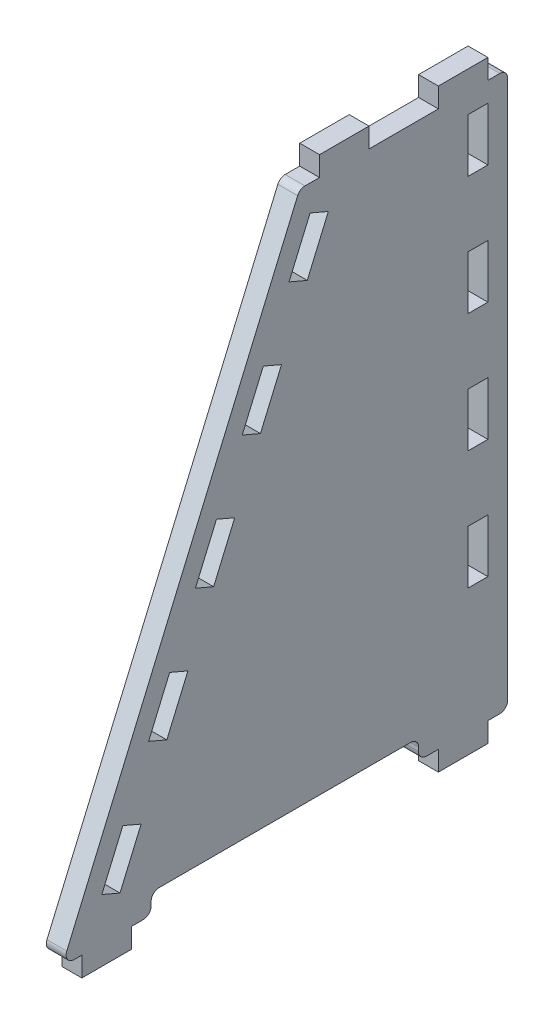
SolidWorks part; units mm, degrees
ref_plane "Front Plane" through (0, 0, 0) normal (0, 0, 1) x (1, 0, 0)
ref_plane "Top Plane" through (0, 0, 0) normal (0, 1, 0) x (1, 0, 0)
ref_plane "Right Plane" through (0, 0, 0) normal (1, 0, 0) x (0, 0, -1)
sketch "Sketch1" plane through (0, 0, 0) normal (1, 0, 0) x (0, 0, -1)
  line L0 (33.3375, 0) -> (-33.3375, 0) construction
  line L1 (-33.3375, 88.9) -> (33.3375, 88.9)
  line L2 (-33.3375, 88.9) -> (-33.3375, -88.9) construction
  line L3 (-33.3375, -88.9) -> (33.3375, -88.9)
  line L4 (33.3375, 88.9) -> (33.3375, -88.9)
  line L5 (26.9875, -88.9) -> (26.9875, -95.25)
  line L6 (-26.9875, 88.9) -> (-11.1125, 88.9)
  line L7 (-26.9875, 88.9) -> (-26.9875, 95.25)
  line L8 (-26.9875, 95.25) -> (-11.1125, 95.25)
  line L9 (-11.1125, 88.9) -> (-11.1125, 95.25)
  line L10 (11.1125, 88.9) -> (26.9875, 88.9)
  line L11 (11.1125, 88.9) -> (11.1125, 95.25)
  line L12 (11.1125, 95.25) -> (26.9875, 95.25)
  line L13 (26.9875, 88.9) -> (26.9875, 95.25)
  line L14 (11.1125, -95.25) -> (26.9875, -95.25)
  line L15 (11.1125, -88.9) -> (11.1125, -95.25)
  line L16 (-33.3375, -88.9) -> (-109.5375, -88.9)
  line L17 (-109.5375, -88.9) -> (-33.3375, 88.9)
  line L18 (-80.9625, -82.55) -> (4.7625, -82.55)
  line L19 (-103.1875, -88.9) -> (-87.3125, -88.9)
  line L20 (-103.1875, -88.9) -> (-103.1875, -95.25)
  line L21 (-103.1875, -95.25) -> (-87.3125, -95.25)
  line L22 (-87.3125, -88.9) -> (-87.3125, -95.25)
  line L23 (-80.9625, -82.55) -> (-80.9625, -88.9)
  line L24 (4.7625, -82.55) -> (4.7625, -88.9)
  point P4 (0, 88.9)
  point P6 (33.3375, 0)
  point P17 (11.1125, 92.075)
  point P29 (-87.3125, -92.075)
  dimension "D1" = 66.675
  dimension "D2" = 177.8
  dimension "D3" = 6.35
  dimension "D4" = 15.875
  dimension "D5" = 22.225
  dimension "D6" = 6.35
  dimension "D7" = 76.2
  dimension "D8" = 114.3
  dimension "D9" = 6.35
  dimension "D10" = 85.725
  dimension "D11" = 6.35
extrude "Boss-Extrude1" add sketch "Sketch1" along normal blind 6.35 contours L18 L24 L3 L4 L1 L17 L16 L23 | L3 L15 L14 L5 | L1 L9 L8 L7 | L1 L13 L12 L11 | L20 L19 L22 L21 region at (0, -8.5198, 20.8552) region at (0, 92.075, 19.05) region at (0, 92.075, -19.05) region at (0, -92.075, -19.05)
sketch "Sketch2" plane through (6.35, 0, 0) normal (1, 0, 0) x (0, 0, -1)
  line L0 (33.3375, 88.9) -> (33.3375, -88.9) construction
  line L1 (20.6375, 82.55) -> (26.9875, 82.55)
  line L2 (20.6375, 82.55) -> (20.6375, 65.405)
  line L3 (20.6375, 65.405) -> (26.9875, 65.405)
  line L4 (26.9875, 82.55) -> (26.9875, 65.405)
  line L5 (26.9875, 88.9) -> (33.3375, 88.9) construction
  line L6 (26.9875, 44.45) -> (26.9875, 27.305)
  line L7 (20.6375, 44.45) -> (26.9875, 44.45)
  line L8 (20.6375, 44.45) -> (20.6375, 27.305)
  line L9 (20.6375, 27.305) -> (26.9875, 27.305)
  line L10 (26.9875, 6.35) -> (26.9875, -10.795)
  line L11 (20.6375, 6.35) -> (26.9875, 6.35)
  line L12 (20.6375, 6.35) -> (20.6375, -10.795)
  line L13 (20.6375, -10.795) -> (26.9875, -10.795)
  line L14 (26.9875, -31.75) -> (26.9875, -48.895)
  line L15 (20.6375, -31.75) -> (26.9875, -31.75)
  line L16 (20.6375, -31.75) -> (20.6375, -48.895)
  line L17 (20.6375, -48.895) -> (26.9875, -48.895)
  line L18 (-30.0023, 80.562) -> (-36.7561, 64.8033)
  line L19 (-36.7561, 64.8033) -> (-30.9195, 62.3019)
  line L20 (-30.9195, 62.3019) -> (-24.1657, 78.0607)
  line L21 (-24.1657, 78.0607) -> (-30.0023, 80.562)
  line L22 (-109.5375, -88.9) -> (-33.3375, 88.9) construction
  line L23 (-45.0106, 45.5426) -> (-51.7644, 29.7839)
  line L24 (-45.9278, 27.2825) -> (-39.1741, 43.0412)
  line L25 (-39.1741, 43.0412) -> (-45.0106, 45.5426)
  line L26 (-51.7644, 29.7839) -> (-45.9278, 27.2825)
  line L27 (-60.019, 10.5232) -> (-66.7727, -5.2356)
  line L28 (-60.9361, -7.7369) -> (-54.1824, 8.0218)
  line L29 (-54.1824, 8.0218) -> (-60.019, 10.5232)
  line L30 (-66.7727, -5.2356) -> (-60.9361, -7.7369)
  line L31 (-75.0273, -24.4962) -> (-81.781, -40.255)
  line L32 (-75.9445, -42.7564) -> (-69.1907, -26.9976)
  line L33 (-69.1907, -26.9976) -> (-75.0273, -24.4962)
  line L34 (-81.781, -40.255) -> (-75.9445, -42.7564)
  line L35 (-90.0356, -59.5157) -> (-96.7894, -75.2744)
  line L36 (-90.9528, -77.7758) -> (-84.199, -62.017)
  line L37 (-84.199, -62.017) -> (-90.0356, -59.5157)
  line L38 (-96.7894, -75.2744) -> (-90.9528, -77.7758)
  line L39 (-30.0023, 80.562) -> (-45.0106, 45.5426) construction
  dimension "D1" = 17.145
  dimension "D2" = 6.35
  dimension "D3" = 6.35
  dimension "D4" = 6.35
  dimension "D6" = 38.1
  dimension "D7" = 6.35
  dimension "D8" = 6.35
  dimension "D9" = 17.145
  dimension "D10" = 6.35
  dimension "D12" = 38.1
  dimension "D5" = 4
  dimension "D11" = 5
extrude "Cut-Extrude1" cut sketch "Sketch2" against normal through all
fillet "Fillet1" radius 2.54 8 edges at (3.175, 88.9, 33.3375) (3.175, 88.9, -33.3375) (3.175, -88.9, -33.3375) (3.175, -88.9, 109.5375) (3.175, -88.9, -4.7625) (3.175, -82.55, -4.7625) (3.175, -82.55, 80.9625) (3.175, -88.9, 80.9625)
